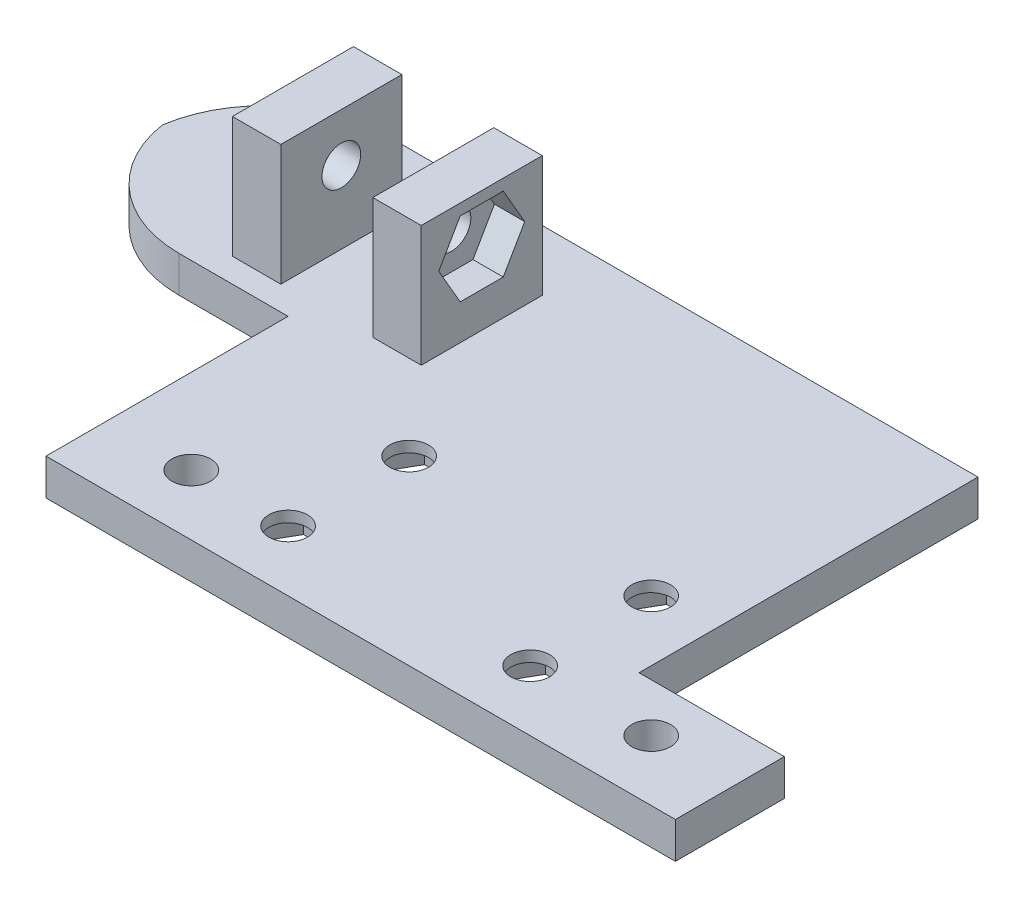
SolidWorks part; units mm, degrees
ref_plane "Front Plane" through (0, 0, 0) normal (0, 0, 1) x (1, 0, 0)
ref_plane "Top Plane" through (0, 0, 0) normal (0, 1, 0) x (1, 0, 0)
ref_plane "Right Plane" through (0, 0, 0) normal (1, 0, 0) x (0, 0, -1)
sketch "Sketch1" plane through (0, 0, 0) normal (0, 1, 0) x (1, 0, 0)
  line L0 (-52, 20) -> (-71, 20)
  line L1 (0, 0) -> (-52, 0)
  line L2 (0, 0) -> (0, 30)
  line L3 (0, 30) -> (-52, 30)
  line L4 (-52, 0) -> (-52, 30)
  line L6 (0, 30) -> (0, 37)
  line L7 (-71, 20) -> (-52, 20)
  line L8 (-71, 20) -> (-71, 30)
  line L9 (-71, 30) -> (-52, 30)
  line L10 (-52, 20) -> (-52, 30)
  line L11 (-71, 30) -> (0, 30)
  line L12 (-71, 30) -> (-71, 37)
  line L13 (-71, 37) -> (0, 37)
  line L14 (0, 30) -> (0, 37)
  line L15 (0, 37) -> (-12, 37)
  line L16 (0, 37) -> (0, 9)
  line L17 (0, 9) -> (-12, 9)
  line L18 (-12, 37) -> (-12, 9)
  dimension "D1" = 52
  dimension "D2" = 19
  dimension "D3" = 20
  dimension "D4" = 28
  dimension "D5" = 12
  dimension "D8" = 30
  dimension "D9" = 7
extrude "Boss-Extrude1" add sketch "Sketch1" along normal blind 3 contours L18 L11 L4 L1 L2 L17 | L9 L8 L0 L4 | L18 L13 L12 L9 L11 region at (-29.8532, 0, -14.133) region at (-61.5, 0, -25) region at (-41.5, 0, -33.5)
sketch "Sketch2" plane through (0, 0, 0) normal (0, -1, 0) x (1, 0, 0)
  line L0 (0, 0) -> (0, -9) construction
  line L1 (-46.1659, -5) -> (5.8341, -5) construction
  line L2 (-52, 0) -> (-52, -20) construction
  line L3 (-43.9637, -15) -> (8.0363, -15) construction
  line L6 (-52, 0) -> (-52, -20) construction
  line L8 (0, 0) -> (-52, 0) construction
  line L9 (-62, -21.3506) -> (-62, -56.3506) construction
  line L10 (-33.507, -5) -> (-35.2535, -1.975)
  line L11 (-35.2535, -1.975) -> (-38.7465, -1.975)
  line L12 (-38.7465, -1.975) -> (-40.493, -5)
  line L13 (-40.493, -5) -> (-38.7465, -8.025)
  line L14 (-38.7465, -8.025) -> (-35.2535, -8.025)
  line L15 (-35.2535, -8.025) -> (-33.507, -5)
  line L16 (-15.2535, -8.025) -> (-13.507, -5)
  line L17 (-13.507, -5) -> (-15.2535, -1.975)
  line L18 (-15.2535, -1.975) -> (-18.7465, -1.975)
  line L19 (-18.7465, -1.975) -> (-20.493, -5)
  line L20 (-20.493, -5) -> (-18.7465, -8.025)
  line L21 (-18.7465, -8.025) -> (-15.2535, -8.025)
  line L22 (-33.507, -15) -> (-35.2535, -11.975)
  line L23 (-35.2535, -11.975) -> (-38.7465, -11.975)
  line L24 (-38.7465, -11.975) -> (-40.493, -15)
  line L25 (-40.493, -15) -> (-38.7465, -18.025)
  line L26 (-38.7465, -18.025) -> (-35.2535, -18.025)
  line L27 (-35.2535, -18.025) -> (-33.507, -15)
  line L28 (-13.507, -15) -> (-15.2535, -11.975)
  line L29 (-15.2535, -11.975) -> (-18.7465, -11.975)
  line L30 (-18.7465, -11.975) -> (-20.493, -15)
  line L31 (-20.493, -15) -> (-18.7465, -18.025)
  line L32 (-18.7465, -18.025) -> (-15.2535, -18.025)
  line L33 (-15.2535, -18.025) -> (-13.507, -15)
  line L36 (-71, -20) -> (-52, -20) construction
  line L38 (-71, -20) -> (-71, -37) construction
  line L39 (-62, -31.993) -> (-58.975, -30.2465)
  line L40 (-58.975, -30.2465) -> (-58.975, -26.7535)
  line L41 (-58.975, -26.7535) -> (-62, -25.007)
  line L42 (-62, -25.007) -> (-65.025, -26.7535)
  line L43 (-65.025, -26.7535) -> (-65.025, -30.2465)
  line L44 (-65.025, -30.2465) -> (-62, -31.993)
  circle A0 centre (-37, -5) radius 3.025 construction
  circle A1 centre (-17, -5) radius 3.025 construction
  circle A2 centre (-37, -15) radius 3.025 construction
  circle A3 centre (-17, -15) radius 3.025 construction
  circle A4 centre (-62, -28.5) radius 3.025 construction
  point P1 (-37, -5)
  point P3 (-17, -15)
  point P4 (-17, -5)
  point P5 (-37, -15)
  point P14 (-7, -5)
  point P15 (-45, -5)
  point P47 (-62, -28.5)
  dimension "D7" = 6.05
  dimension "D8" = 6.05
  dimension "D9" = 6.05
  dimension "D10" = 6.05
  dimension "D13" = 6.05
  dimension "D14" = 7
  dimension "D1" = 15
  dimension "D2" = 17
  dimension "D3" = 17
  dimension "D4" = 15
  dimension "D5" = 5
  dimension "D6" = 15
  dimension "D11" = 8.5
  dimension "D12" = 38
  dimension "D15" = 9
extrude "Cut-Extrude1" cut sketch "Sketch2" against normal blind 2.1 contours L26 L27 L22 L23 L24 L25 | L32 L33 L28 L29 L30 L31 | L20 L21 L16 L17 L18 L19 | L14 L15 L10 L11 L12 L13 | L43 L44 L39 L40 L41 L42 region at (-37, 0, -5) region at (-17, 0, -5) region at (-37, 0, -15) region at (-17, 0, -15) region at (-62, 0, -28.5)
hole_wizard "Hole1" positions "3DSketch1" profile "Sketch3" legacy end condition through all
sketch3d "3DSketch1"
  point P0 (-37, 0, -15)
  point P3 (-37, 0, -5)
  point P6 (-17, 0, -5)
  point P9 (-17, 0, -15)
  point P16 (-62, 0, -28.5)
  point P19 (-45, 0, -5)
  point P22 (-7, 0, -5)
sketch "Sketch3" plane through (-37, 0, -15) normal (1, 0, 0) x (0, 0, -1)
  line L0 (0, 0) -> (0, 3)
  line L1 (0, 3) -> (1.6, 3)
  line L2 (1.6, 3) -> (1.6, 0)
  line L3 (1.6, 0) -> (0, 0)
  line L4 (0, 110) -> (0, -10) construction
  dimension "Diameter" = 3.2
  dimension "Depth" = 3
sketch "Sketch4" plane through (0, 3, 0) normal (0, 1, 0) x (1, 0, 0)
  line L0 (-47, 32) -> (-47, 22)
  line L1 (-47, 22) -> (-43, 22)
  line L2 (-54.6, 32) -> (-54.6, 22)
  line L3 (-47, 32) -> (-43, 32)
  line L6 (-43, 32) -> (-43, 22)
  line L7 (-54.6, 22) -> (-58.6, 22)
  line L10 (-58.6, 22) -> (-58.6, 32)
  line L11 (-58.6, 32) -> (-54.6, 32)
  line L13 (-71, 37) -> (-12, 37) construction
  line L14 (0, 0) -> (0, 9) construction
  dimension "D1" = 7.6
  dimension "D2" = 43
  dimension "D3" = 4
  dimension "D4" = 4
  dimension "D5" = 5
  dimension "D6" = 10
  dimension "D7" = 10
extrude "Boss-Extrude2" add sketch "Sketch4" along normal blind 10 contours L11 L10 L7 L2 | L6 L3 L0 L1 region at (-45, 3, -27) region at (-56.6, 3, -27)
sketch "Sketch5" plane through (-58.6, 0, 0) normal (-1, 0, 0) x (0, 0, 1)
  line L0 (-32, 13) -> (-22, 13) construction
  line L1 (-27, 13) -> (-27, 9) construction
  point P0 (-27, 9)
  dimension "D1" = 4
hole_wizard "Hole2" positions "3DSketch2" profile "Sketch7" legacy end condition through all
sketch3d "3DSketch2"
  point P0 (-58.6, 9, -27)
sketch "Sketch7" plane through (-58.6, 9, -27) normal (0, 1, 0) x (0, 0, 1)
  line L0 (0, 0) -> (0, 58.6)
  line L1 (0, 58.6) -> (1.6, 58.6)
  line L2 (1.6, 58.6) -> (1.6, 1.7461)
  line L3 (1.6, 1.7461) -> (3.2, 0)
  line L4 (3.2, 0) -> (0, 0)
  line L5 (0, -6.4453) -> (0, 115.525) construction
  line L6 (-1.6, 1.7461) -> (-3.2, 0) construction
  dimension "Diameter" = 3.2
  dimension "Depth" = 58.6
  dimension "C-Sink Angle" = 85
  dimension "C-Sink Diameter" = 6.4
sketch "Sketch8" plane through (-43, 0, 0) normal (1, 0, 0) x (0, 0, -1)
  line L0 (32, 13) -> (22, 13) construction
  line L1 (25.2246, 5.925) -> (28.7754, 5.925)
  line L2 (28.7754, 5.925) -> (30.5507, 9)
  line L3 (30.5507, 9) -> (28.7754, 12.075)
  line L4 (28.7754, 12.075) -> (25.2246, 12.075)
  line L5 (25.2246, 12.075) -> (23.4493, 9)
  line L6 (23.4493, 9) -> (25.2246, 5.925)
  circle A0 centre (27, 9) radius 1.6 construction
  circle A1 centre (27, 9) radius 3.075 construction
  point P0 (27, 9)
  circle M7 centre (27, 9) radius 1.6
  dimension "D1" = 6.15
extrude "Cut-Extrude2" cut sketch "Sketch8" against normal blind 2.5 contours L5 L6 L1 L2 L3 L4 M7 region at (-43, 7.5095, -24.4183)
fillet "Fillet1" radius 10 2 edges at (-71, 1.5, -37) (-71, 1.5, -20)
